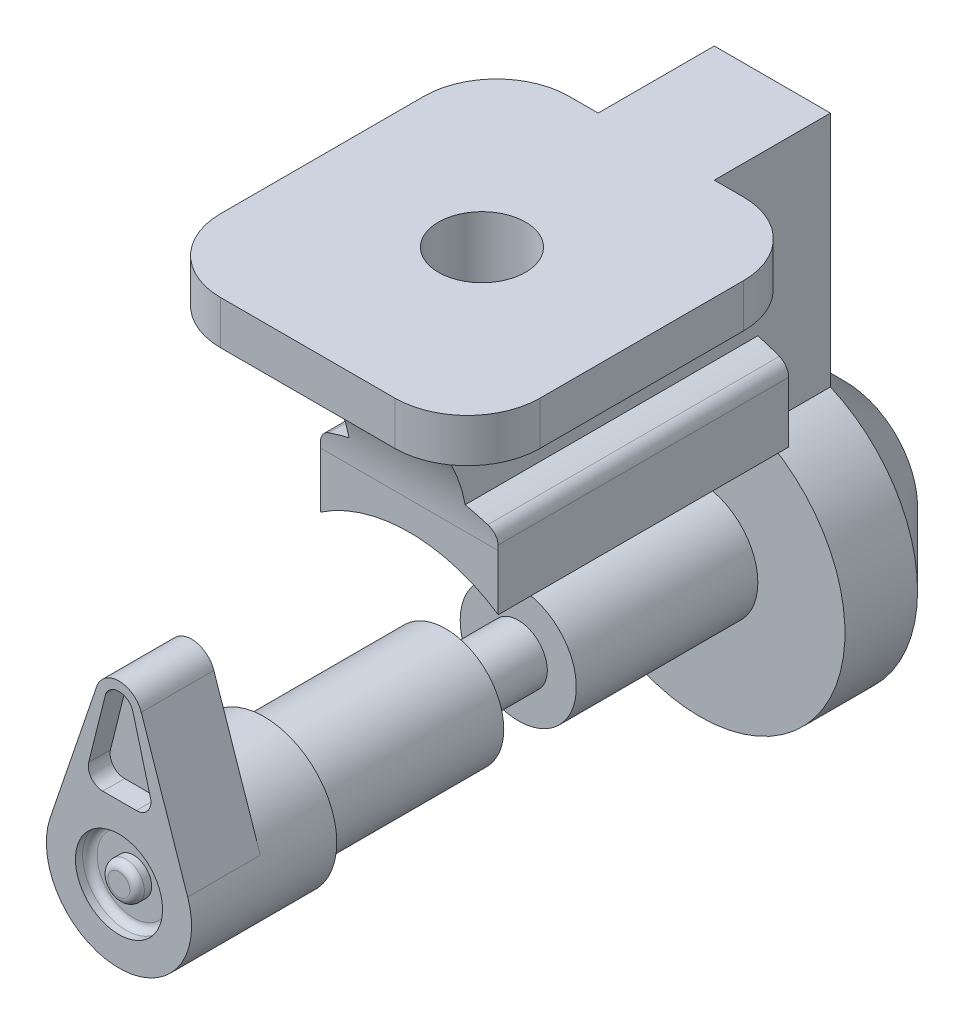
SolidWorks part; units mm, degrees
ref_plane "前视基准面" through (0, 0, 0) normal (0, 0, 1) x (1, 0, 0)
ref_plane "上视基准面" through (0, 0, 0) normal (0, 1, 0) x (1, 0, 0)
ref_plane "右视基准面" through (0, 0, 0) normal (1, 0, 0) x (0, 0, -1)
sketch "草图1" plane through (0, 0, 0) normal (0, 0, 1) x (1, 0, 0)
  circle A0 centre (0, 0) radius 2
extrude "凸台-拉伸1" add sketch "草图1" along normal blind 30
sketch "草图2" plane through (0, 0, 30) normal (0, 0, 1) x (1, 0, 0)
  circle A0 centre (0, 0) radius 4
extrude "凸台-拉伸2" add sketch "草图2" against normal blind 12.5
sketch "草图3" plane through (0, 0, 0) normal (0, 0, -1) x (-1, 0, 0)
  circle A0 centre (0, 0) radius 4
extrude "凸台-拉伸3" add sketch "草图3" against normal blind 12.5
sketch "草图4" plane through (0, 0, 30) normal (0, 0, 1) x (1, 0, 0)
  circle A0 centre (0, 0) radius 5
extrude "凸台-拉伸4" add sketch "草图4" along normal blind 10
sketch "草图5" plane through (0, 0, 40) normal (0, 0, 1) x (1, 0, 0)
  line L0 (-1.5366, 11.0258) -> (-4.7345, 1.6076)
  line L1 (1.5366, 11.0258) -> (4.7345, 1.6076)
  arc A0 (1.5366, 11.0258) -> (-1.5366, 11.0258) centre (0, 10.504) ccw
  circle A1 centre (0, 0) radius 5 construction
  arc A2 (-4.7345, 1.6076) -> (4.7345, 1.6076) centre (0, 0) ccw
extrude "凸台-拉伸5" add sketch "草图5" against normal blind 5
sketch "草图6" plane through (0, 0, 0) normal (0, 0, -1) x (-1, 0, 0)
  circle A0 centre (0, 0) radius 4
extrude "凸台-拉伸6" add sketch "草图6" along normal blind 5
sketch "草图7" plane through (0, 0, -5) normal (0, 0, -1) x (-1, 0, 0)
  line L0 (-4, 0) -> (-4, 10.5)
  line L1 (-4, 10.5) -> (4, 10.5)
  line L2 (4, 10.5) -> (4, 0)
  line L3 (-4, 0) -> (4, 0)
  circle A0 centre (0, 0) radius 4 construction
  circle A1 centre (0, 0) radius 4 construction
extrude "凸台-拉伸7" add sketch "草图7" against normal blind 5
sketch "草图8" plane through (0, 10.5, 0) normal (0, 1, 0) x (1, 0, 0)
  line L0 (-4, 5) -> (4, 5)
  line L1 (4, 5) -> (4, 0)
  line L2 (4, 0) -> (-4, 0)
  line L3 (-4, 0) -> (-4, 5)
extrude "凸台-拉伸8" add sketch "草图8" along normal blind 15
sketch "草图9" plane through (0, 0, 0) normal (0, 0, 1) x (1, 0, 0)
  line L0 (-4, 14.7161) -> (-4, 25.5)
  line L2 (-4, 0) -> (-4, 25.5) construction
  line L3 (-4, 25.5) -> (4, 25.5)
  line L4 (4, 25.5) -> (4, 14.7161)
  line L5 (4, 25.5) -> (4, 0) construction
  line L7 (-6.1206, 13.9678) -> (-6.1206, 9.1399)
  line L8 (6.1206, 13.9678) -> (6.1206, 9.1399)
  arc A2 (6.1206, 9.1399) -> (-6.1206, 9.1399) centre (0, 0) ccw
  arc A3 (6.1206, 13.9678) -> (4, 14.7161) centre (0, 0) ccw
  arc A4 (-4, 14.7161) -> (-6.1206, 13.9678) centre (0, 0) ccw
extrude "凸台-拉伸10" add sketch "草图9" along normal blind 20
sketch "草图11" plane through (0, 0, 0) normal (0, 1, 0) x (1, 0, 0)
  line L0 (0, 5) -> (0, 10)
  line L1 (4, 5) -> (-4, 5) construction
  line L2 (0, 10) -> (-5, 10)
  line L3 (-5, 10) -> (-10, 5)
  line L4 (-10, 5) -> (0, 5)
revolve "旋转1" add sketch "草图11" angle 360 about L0
sketch "草图12" plane through (0, 0, -5) normal (0, 0, 1) x (1, 0, 0)
  circle A0 centre (0, 0) radius 10
extrude "凸台-拉伸11" add sketch "草图12" along normal blind 5
sketch "草图13" plane through (0, 0, 40) normal (0, 0, 1) x (1, 0, 0)
  circle A0 centre (0, 0) radius 3
extrude "切除-拉伸1" cut sketch "草图13" against normal blind 1
fillet "圆角1" radius 0.5 1 edges at (3, 0, 39)
sketch "草图14" plane through (0, 0, 40) normal (0, 0, 1) x (1, 0, 0)
  line L1 (0, 5) -> (-2.3929, 5)
  line L2 (-2.3929, 5) -> (-0.9229, 10.889)
  line L3 (0, 5) -> (2.5, 5)
  line L4 (2.5, 5) -> (0.9663, 10.7613)
  arc A0 (0.9663, 10.7613) -> (-0.9956, 10.598) centre (0, 10.504) ccw
extrude "切除-拉伸2" cut sketch "草图14" against normal blind 1.5 contours L4 A0 L2 L1 L3 region at (0.0315, 7.647, 40)
fillet "圆角2" radius 1 2 edges at (2.5, 5, 39.25) (-2.3929, 5, 39.25)
fillet "圆角3" radius 1 2 edges at (-6.1206, 13.9678, 10) (6.1206, 13.9678, 10)
sketch "草图15" plane through (0, 25.5, 0) normal (0, 1, 0) x (1, 0, 0)
  circle A0 centre (0, -15) radius 3
extrude "切除-拉伸3" cut sketch "草图15" against normal blind 10
sketch "草图16" plane through (0, 0, 39) normal (0, 0, 1) x (1, 0, 0)
  circle A0 centre (0, 0) radius 1.25
extrude "凸台-拉伸12" add sketch "草图16" along normal blind 1
fillet "圆角4" radius 0.5 1 edges at (1.25, 0, 40)
sketch "草图17" plane through (0, 0, 20) normal (0, 0, 1) x (1, 0, 0)
  line L0 (-4, 25.5) -> (4, 25.5)
  line L1 (4, 25.5) -> (4, 22.5)
  line L2 (4, 14.7161) -> (4, 25.5) construction
  line L3 (4, 22.5) -> (-4, 22.5)
  line L4 (-4, 25.5) -> (-4, 14.7161) construction
  line L5 (-4, 22.5) -> (-4, 25.5)
extrude "凸台-拉伸13" add sketch "草图17" along normal blind 7
fillet "圆角5" radius 10 1 edges at (0, 22.5, 20)
sketch "草图18" plane through (-4, 0, 0) normal (-1, 0, 0) x (0, 0, 1)
  line L0 (27, 25.5) -> (27, 22.5)
  line L5 (27, 25.5) -> (3, 25.5)
  line L6 (-5, 25.5) -> (27, 25.5) construction
  line L7 (3, 25.5) -> (3, 22.5)
  line L8 (3, 22.5) -> (27, 22.5)
extrude "凸台-拉伸14" add sketch "草图18" along normal blind 7
sketch "草图19" plane through (4, 0, 0) normal (1, 0, 0) x (0, 0, -1)
  line L0 (-27, 25.5) -> (-27, 22.5)
  line L1 (-27, 22.5) -> (-27, 25.5) construction
  line L2 (-27, 22.5) -> (-3, 22.5)
  line L3 (-3, 22.5) -> (-3, 25.5)
  line L4 (-27, 25.5) -> (5, 25.5) construction
  line L5 (-3, 25.5) -> (-27, 25.5)
extrude "凸台-拉伸15" add sketch "草图19" along normal blind 7
fillet "圆角6" radius 5 4 edges at (-11, 24, 3) (11, 24, 3) (11, 24, 27) (-11, 24, 27)
